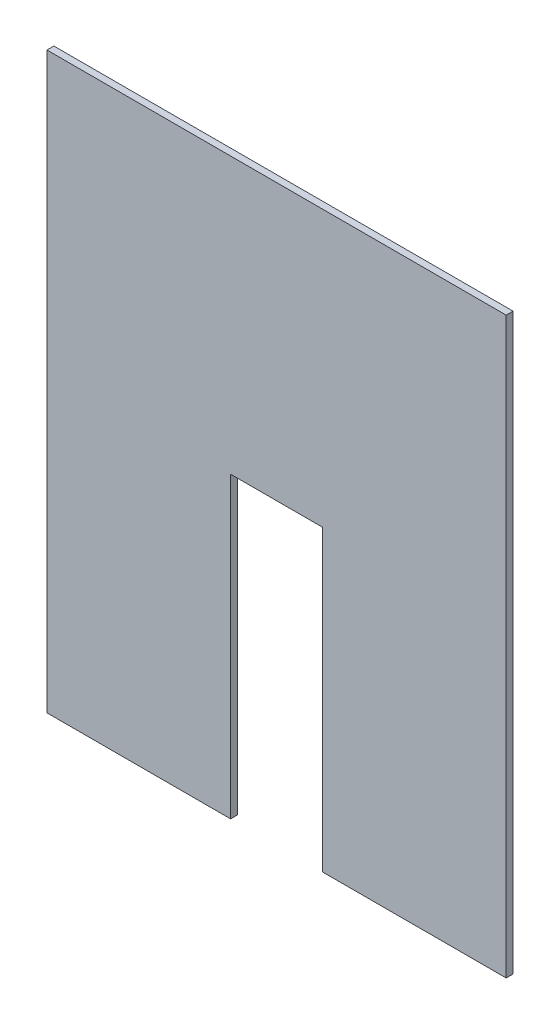
SolidWorks part; units mm, degrees
material "Balsa"
ref_plane "Plano frontal" through (0, 0, 0) normal (0, 0, 1) x (1, 0, 0)
ref_plane "Plano superior" through (0, 0, 0) normal (0, 1, 0) x (1, 0, 0)
ref_plane "Plano direito" through (0, 0, 0) normal (1, 0, 0) x (0, 0, -1)
sketch "Esboço1" plane through (0, 0, 0) normal (0, 0, 1) x (1, 0, 0)
  line L0 (0, -125) -> (0, 5) construction
  line L1 (-100, 125) -> (100, 125)
  line L2 (-100, 125) -> (-100, -125)
  line L3 (-100, -125) -> (-20, -125)
  line L4 (100, 125) -> (100, -125)
  line L5 (-100, 125) -> (100, -125) construction
  line L6 (-100, -125) -> (100, 125) construction
  line L7 (20, -125) -> (20, 5)
  line L8 (-20, -125) -> (-20, 5)
  line L10 (20, 5) -> (-20, 5)
  line L11 (20, -125) -> (100, -125)
  point P0 (0, 0)
  dimension "D1" = 200
  dimension "D2" = 250
  dimension "D5" = 130
  dimension "D3" = 20
  dimension "D4" = 20
extrude "Ressalto-extrusão1" add sketch "Esboço1" along normal blind 3
